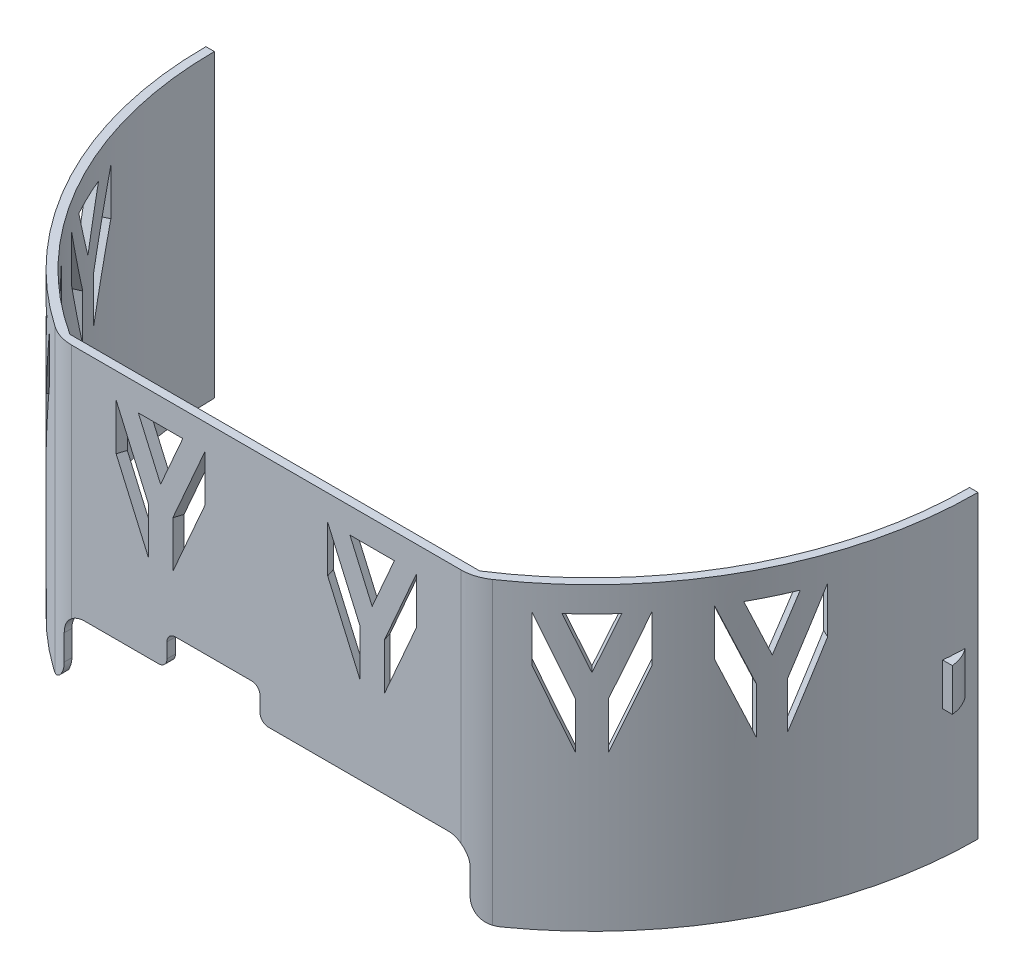
SolidWorks part; units mm, degrees
ref_plane "Front Plane" through (0, 0, 0) normal (0, 0, 1) x (1, 0, 0)
ref_plane "Top Plane" through (0, 0, 0) normal (0, 1, 0) x (1, 0, 0)
ref_plane "Right Plane" through (0, 0, 0) normal (1, 0, 0) x (0, 0, -1)
sketch "Sketch1" plane through (0, 0, 0) normal (0, 1, 0) x (1, 0, 0)
  line L0 (0, 124.168) -> (0, -125.7458) construction
  line L1 (-136.0011, 0) -> (148.623, 0) construction
  line L2 (-48.4715, -75) -> (48.4715, -75)
  line L3 (-49.058, -77) -> (49.058, -77)
  arc A0 (48.4715, -75) -> (-48.4715, -75) centre (0, 0) ccw
  arc A1 (49.058, -77) -> (-49.058, -77) centre (0, 0) ccw
  dimension "D1" = 178.6
  dimension "D3" = 182.6
  dimension "D2" = 75
  dimension "D4" = 77
extrude "Boss-Extrude1" add sketch "Sketch1" along normal blind 71
fillet "Fillet1" radius 10 2 edges at (-49.058, 35.5, 77) (49.058, 35.5, 77)
sketch "Sketch2" plane through (0, 0, 77) normal (0, 0, 1) x (1, 0, 0)
  line L0 (0, 94.4811) -> (0, -36.6428) construction
  line L1 (46.051, 0) -> (51.7153, 0) construction
  line L2 (-48, 16) -> (48, 16)
  line L4 (-48, 16) -> (-48, 0)
  line L5 (-48, 0) -> (48, 0)
  line L6 (48, 16) -> (48, 0)
  line L7 (-48, 16) -> (48, 0) construction
  line L8 (-48, 0) -> (48, 16) construction
  line L9 (-46.051, 71) -> (46.051, 71) construction
  point P3 (0, 8)
  dimension "D1" = 55
  dimension "D2" = 96
extrude "Cut-Extrude1" cut sketch "Sketch2" against normal blind 5
sketch "Sketch3" plane through (0, 0, 77) normal (0, 0, 1) x (1, 0, 0)
  line L0 (0, 94.4811) -> (0, -26.607) construction
  line L1 (46.051, 16) -> (-46.051, 16) construction
  line L2 (-23.5, 16) -> (-1.5, 16)
  line L3 (-23.5, 16) -> (-23.5, 23.5)
  line L4 (-23.5, 23.5) -> (-1.5, 23.5)
  line L5 (-1.5, 16) -> (-1.5, 23.5)
  dimension "D1" = 22
  dimension "D2" = 7.5
  dimension "D3" = 1.5
extrude "Cut-Extrude2" cut sketch "Sketch3" against normal blind 5
fillet "Fillet2" radius 5 4 edges at (-48, 16, 75.9041) (-48, 0, 75.9041) (48, 16, 75.9041) (48, 0, 75.9041)
fillet "Fillet3" radius 2 4 edges at (-1.5, 16, 76) (-1.5, 23.5, 76) (-23.5, 16, 76) (-23.5, 23.5, 76)
sketch "Sketch4" plane through (0, 0, 0) normal (0, 0, 1) x (1, 0, 0)
  line L0 (0, 103.2008) -> (0, -37.4655) construction
  line L1 (-5, 65) -> (5, 65)
  line L2 (-5, 65) -> (0, 53)
  line L3 (0, 53) -> (5, 65)
  line L8 (-46.051, 71) -> (46.051, 71) construction
  line L9 (-10, 65) -> (-2.75, 47.6)
  line L10 (-2.75, 47.6) -> (-2.75, 36.6)
  line L11 (-2.75, 36.6) -> (-10, 54)
  line L12 (-10, 54) -> (-10, 65)
  line L13 (10, 65) -> (2.75, 47.6)
  line L14 (2.75, 47.6) -> (2.75, 36.6)
  line L15 (2.75, 36.6) -> (10, 54)
  line L16 (10, 54) -> (10, 65)
  point P6 (0, 65)
  dimension "D1" = 10
  dimension "D2" = 6
  dimension "D3" = 5
  dimension "D4" = 11
  dimension "D5" = 12
  dimension "D6" = 2.75
extrude "Cut-Extrude3" cut sketch "Sketch4" against normal blind 132
pattern_circular "CirPattern1" count 20 over 360 about axis through (0, 71, 0) along (0, 1, 0) skipping 1, 2, 3, 4, 5, 6, 7, 8, 10, 12, 13, 14, 15, 16, 17, 18, 19 of "Cut-Extrude3"
pattern_circular "CirPattern2" count 16 over 360 about axis through (0, 71, 0) along (0, 1, 0) skipping 1, 2, 3, 4, 5, 7, 8, 9, 11, 12, 13, 14, 15 of "Cut-Extrude3"
pattern_circular "CirPattern3" count 28 over 360 about axis through (0, 71, 0) along (0, 1, 0) skipping 1, 2, 3, 4, 5, 6, 7, 8, 10, 11, 12, 13, 14, 15, 16, 17, 18, 20, 21, 22, 23, 24, 25, 26, 27 of "Cut-Extrude3"
sketch "Sketch5" plane through (0, 0, 77) normal (0, 0, 1) x (1, 0, 0)
  line L0 (0, 101.7201) -> (0, -38.7816) construction
  line L1 (-5, 65) -> (5, 65)
  line L2 (-5, 65) -> (0, 53)
  line L3 (0, 53) -> (5, 65)
  line L4 (-10, 65) -> (-2.75, 47.6)
  line L5 (-2.75, 47.6) -> (-2.75, 36.6)
  line L6 (-2.75, 36.6) -> (-10, 54)
  line L7 (-10, 54) -> (-10, 65)
  line L8 (-46.051, 71) -> (46.051, 71) construction
  line L9 (10, 65) -> (2.75, 47.6)
  line L10 (2.75, 47.6) -> (2.75, 36.6)
  line L11 (2.75, 36.6) -> (10, 54)
  line L12 (10, 54) -> (10, 65)
  point P6 (0, 65)
  dimension "D1" = 10
  dimension "D2" = 5
  dimension "D3" = 11
  dimension "D4" = 2.75
  dimension "D5" = 28.4
  dimension "D6" = 6
  dimension "D7" = 5
  dimension "D8" = 2.75
  dimension "D9" = 12
extrude "Boss-Extrude2" add sketch "Sketch5" against normal blind 5
sketch "Sketch6" plane through (0, 0, 0) normal (0, 1, 0) x (1, 0, 0)
  line L0 (-100.8658, 0) -> (109.8927, 0) construction
  line L1 (-46.051, -77) -> (46.051, -77) construction
  line L3 (-100.8658, 0) -> (109.8927, 0)
  line L4 (-100.8658, 0) -> (-100.8658, 95.751)
  line L5 (-100.8658, 95.751) -> (109.8927, 95.751)
  line L6 (109.8927, 0) -> (109.8927, 95.751)
  dimension "D1" = 77
extrude "Cut-Extrude4" cut sketch "Sketch6" along normal blind 92
ref_plane "Plane1" through (89.3, 0, 0) normal (-1, 0, 0) x (0, 0, 1)
sketch "Sketch7" plane through (89.3, 0, 0) normal (-1, 0, 0) x (0, 0, 1)
  line L0 (75.2411, 71) -> (0, 71) construction
  line L1 (8, 40.5) -> (3, 40.5)
  line L2 (8, 40.5) -> (8, 30.5)
  line L3 (8, 30.5) -> (3, 30.5)
  line L4 (3, 40.5) -> (3, 30.5)
  line L5 (0, 71) -> (0, 0) construction
  dimension "D1" = 5
  dimension "D2" = 10
  dimension "D3" = 30.5
  dimension "D4" = 3
extrude "Boss-Extrude3" add sketch "Sketch7" against normal blind 4
ref_plane "Plane2" through (-89.3, 0, 0) normal (1, 0, 0) x (0, 0, -1)
sketch "Sketch8" plane through (-89.3, 0, 0) normal (1, 0, 0) x (0, 0, -1)
  line L0 (0, 71) -> (-75.2411, 71) construction
  line L1 (-3, 40.5) -> (-8, 40.5)
  line L2 (-3, 40.5) -> (-3, 30.5)
  line L3 (-3, 30.5) -> (-8, 30.5)
  line L4 (-8, 40.5) -> (-8, 30.5)
  line L5 (0, 0) -> (0, 71) construction
  dimension "D1" = 5
  dimension "D2" = 10
  dimension "D3" = 30.5
  dimension "D4" = 3
extrude "Boss-Extrude5" add sketch "Sketch8" against normal blind 4
fillet "Fillet5" radius 10 2 edges at (-93.3, 35.5, 3) (93.3, 35.5, 3)
equation "\"D5@Sketch4\"=20-\"D2@Sketch4\"-2"
equation "\"D9@Sketch5\"=20-\"D6@Sketch5\"-2"
